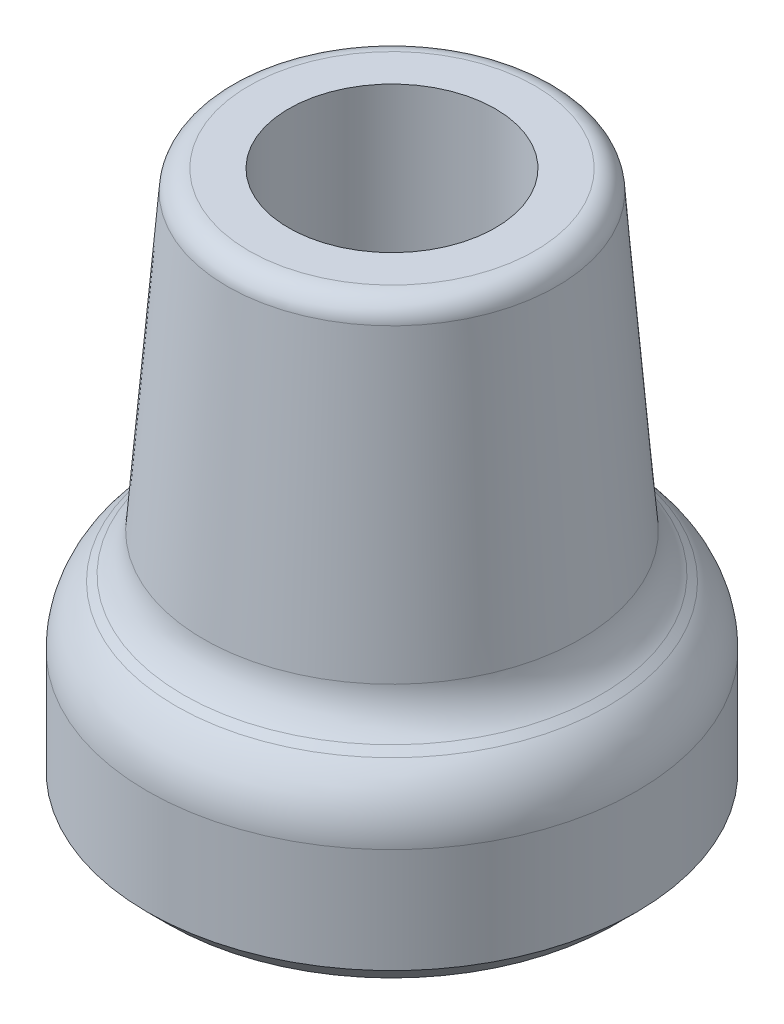
SolidWorks part; units mm, degrees
material "Rubber"
ref_plane "Спереди" through (0, 0, 0) normal (0, 0, 1) x (1, 0, 0)
ref_plane "Сверху" through (0, 0, 0) normal (0, 1, 0) x (1, 0, 0)
ref_plane "Справа" through (0, 0, 0) normal (1, 0, 0) x (0, 0, -1)
sketch "Эскиз1" plane through (0, 0, 0) normal (0, 0, 1) x (1, 0, 0)
  line L0 (0, 0) -> (0, 173.285) construction
  line L1 (0, 20) -> (-9.5, 20)
  line L2 (-9.5, 20) -> (-9.5, 50)
  line L3 (-9.5, 50) -> (-15, 50)
  line L4 (-15, 50) -> (-17.5, 19)
  line L5 (-17.5, 19) -> (-22.5, 15)
  line L6 (-22.5, 15) -> (-22.5, 0)
  line L7 (-22.5, 0) -> (0, 0)
  line L8 (0, 0) -> (0, 20)
  dimension "D1" = 19
  dimension "D2" = 30
  dimension "D3" = 15
  dimension "D4" = 45
  dimension "D5" = 30
  dimension "D6" = 35
  dimension "D7" = 4
  dimension "D8" = 50
revolve "Повернуть1" add sketch "Эскиз1" angle 360 about L0
fillet "Скругление1" radius 2 1 edges at (0, 50, -15)
fillet "Скругление2" radius 5 1 edges at (0, 19, -17.5)
fillet "Скругление3" radius 7 1 edges at (0, 15, -22.5)
chamfer "Фаска1" distance 2 angle 45 1 edges at (0, 0, -22.5)
fillet "Скругление4" radius 1 1 edges at (0, 20, -9.5)
